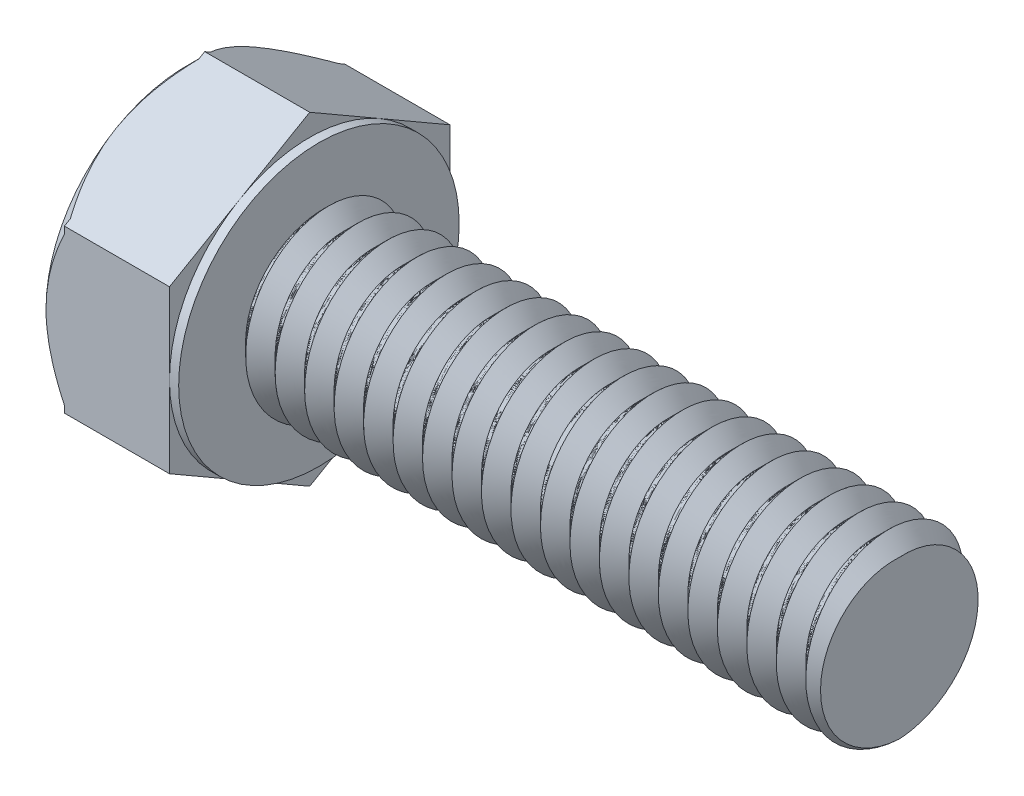
SolidWorks part; units mm, degrees
material "Plain Carbon Steel"
ref_plane "Front Plane" through (0, 0, 0) normal (0, 0, 1) x (1, 0, 0)
ref_plane "Top Plane" through (0, 0, 0) normal (0, 1, 0) x (1, 0, 0)
ref_plane "Right Plane" through (0, 0, 0) normal (1, 0, 0) x (0, 0, -1)
sketch "Sketch3" plane through (0, 0, 0) normal (1, 0, 0) x (0, 0, -1)
  line L1 (0, -4.395) -> (3.8062, -2.1975)
  line L2 (3.8062, -2.1975) -> (3.8062, 2.1975)
  line L3 (3.8062, 2.1975) -> (0, 4.395)
  line L4 (0, 4.395) -> (-3.8062, 2.1975)
  line L5 (-3.8062, 2.1975) -> (-3.8062, -2.1975)
  line L6 (-3.8062, -2.1975) -> (0, -4.395)
  circle A0 centre (0, 0) radius 3.8062 construction
  dimension "D1" = 8.79
extrude "Boss-Extrude1" add sketch "Sketch3" along normal mid plane 3.35
sketch "Sketch4" plane through (1.675, 0, 0) normal (1, 0, 0) x (0, 0, -1)
  circle A0 centre (0, 0) radius 2.5
  dimension "D1" = 5
extrude "Boss-Extrude2" add sketch "Sketch4" along normal blind 16
sketch "Sketch5" plane through (0, 0, 0) normal (0, 0, 1) x (1, 0, 0)
  line L0 (18.2407, 2.5) -> (17.675, 1.9343)
  line L1 (17.675, 1.9343) -> (17.1093, 2.5)
  line L2 (17.675, 2.5) -> (1.675, 2.5) construction
  line L3 (17.1093, 2.5) -> (17.675, 3.0657)
  line L4 (17.675, 3.0657) -> (18.2407, 2.5)
  line L5 (17.675, -2.5) -> (17.675, 2.5) construction
  dimension "D1" = 45
  dimension "D2" = 0.8
sketch "Sketch6" plane through (17.675, 0, 0) normal (1, 0, 0) x (0, 0, -1)
  circle A0 centre (0, 0) radius 2.5
curve "Helix/Spiral1" pitch 0.8 height 16 radius 2.5 centre (17.675, 0, 0) axis (-1, 0, 0) start towards (0, 0.7071, 0.7071)
sweep "Cut-Sweep1" cut profiles "Sketch5" path "Helix/Spiral1" align with end faces yes
sketch "Sketch7" plane through (-1.675, 0, 0) normal (-1, 0, 0) x (0, 0, 1)
  circle A0 centre (0, 0) radius 3.8062
extrude "Cut-Extrude3" cut sketch "Sketch7" against normal blind 0.5 draft 45 flip side to cut
sketch "Sketch8" plane through (1.675, 0, 0) normal (1, 0, 0) x (0, 0, -1)
  circle A0 centre (0, 0) radius 3.8062
extrude "Boss-Extrude3" add sketch "Sketch8" along normal blind 0.25
